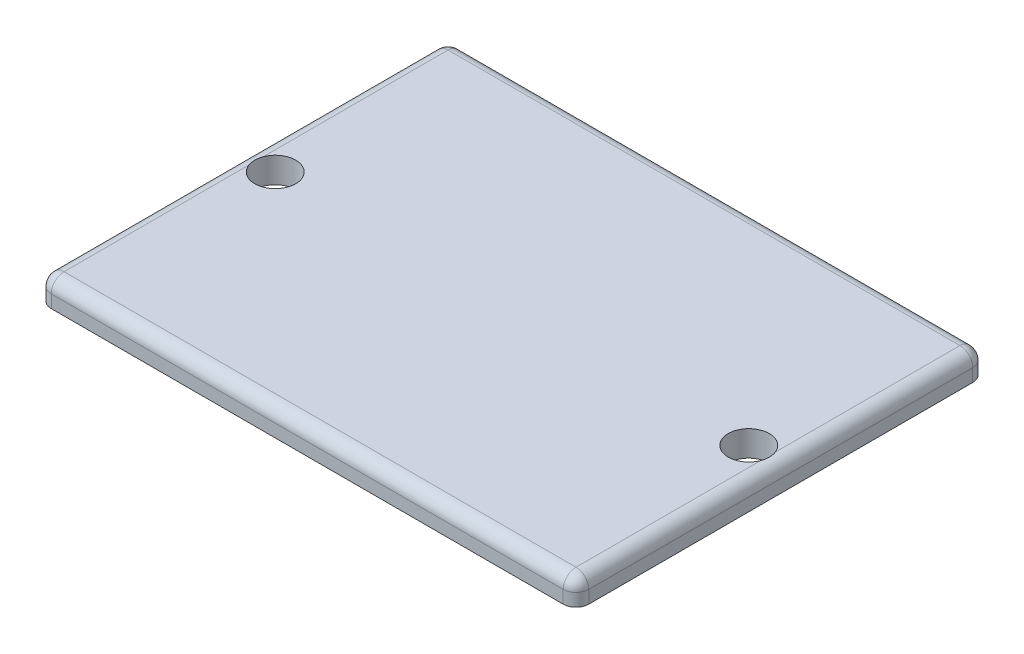
SolidWorks part; units mm, degrees
ref_plane "Front Plane" through (0, 0, 0) normal (0, 0, 1) x (1, 0, 0)
ref_plane "Top Plane" through (0, 0, 0) normal (0, 1, 0) x (1, 0, 0)
ref_plane "Right Plane" through (0, 0, 0) normal (1, 0, 0) x (0, 0, -1)
sketch "Sketch1" plane through (0, 0, 0) normal (0, 1, 0) x (1, 0, 0)
  line L0 (-21, 0) -> (21, 0) construction
  line L1 (-21, -16) -> (21, -16)
  line L2 (-21, -16) -> (-21, 16)
  line L3 (-21, 16) -> (21, 16)
  line L4 (21, -16) -> (21, 16)
  line L5 (-21, -16) -> (21, 16) construction
  line L6 (-21, 16) -> (21, -16) construction
  line L7 (0, 16) -> (0, -16) construction
  circle A0 centre (-18.5, 0) radius 1.6
  circle A1 centre (18.5, 0) radius 1.6
  point P0 (0, 0)
  dimension "D3" = 3.2
  dimension "D1" = 32
  dimension "D2" = 42
  dimension "D4" = 37
extrude "Boss-Extrude1" add sketch "Sketch1" along normal blind 2
fillet "Fillet1" radius 1 8 edges at (0, 2, 16) (-21, 2, 0) (0, 2, -16) (21, 2, 0) (21, 1, -16) (-21, 1, -16) (-21, 1, 16) (21, 1, 16)
